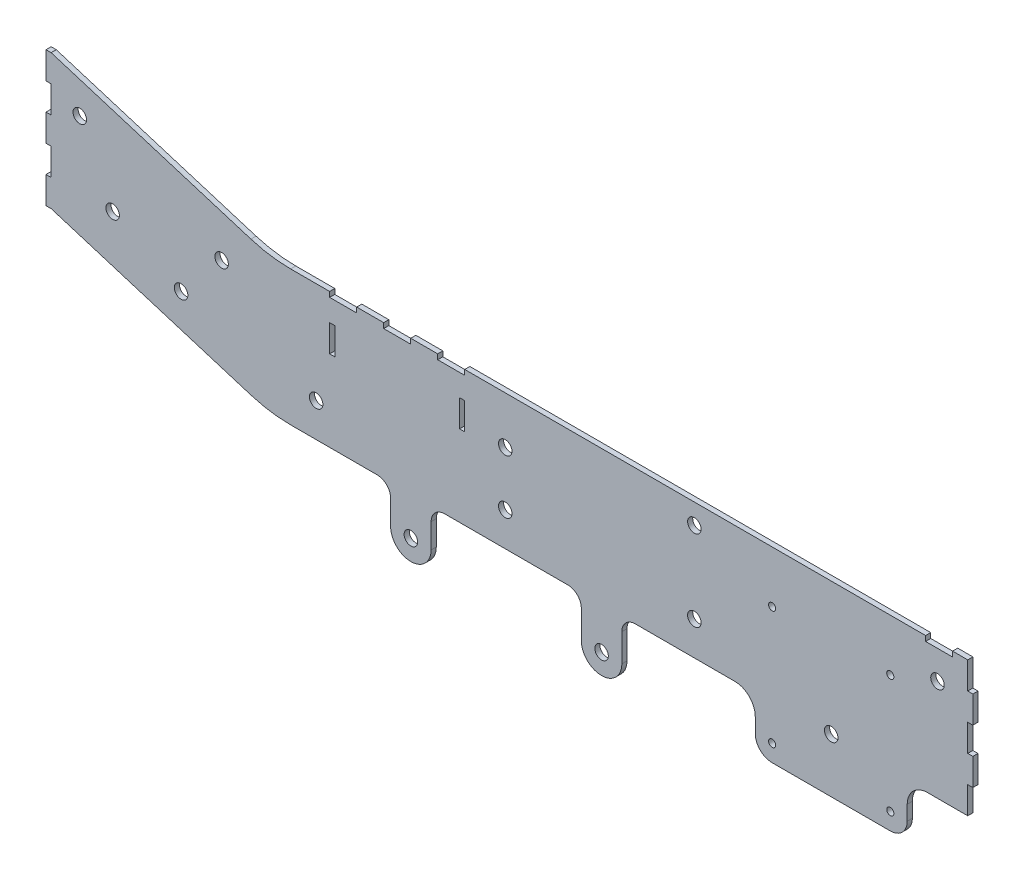
SolidWorks part; units mm, degrees
material "1060 Alloy"
ref_plane "Front Plane" through (0, 0, 0) normal (0, 0, 1) x (1, 0, 0)
ref_plane "Top Plane" through (0, 0, 0) normal (0, 1, 0) x (1, 0, 0)
ref_plane "Right Plane" through (0, 0, 0) normal (1, 0, 0) x (0, 0, -1)
sketch "Sketch2" plane through (0, 0, 0) normal (0, 0, 1) x (1, 0, 0)
  line L41 (-214.6997, -160.1998) -> (-26.8739, -218.0697)
  line L42 (10.5206, -223.6998) -> (91.8093, -223.6998)
  line L43 (104.5093, -236.3998) -> (104.5093, -259.4448)
  line L44 (142.6093, -259.4448) -> (142.6093, -236.3998)
  line L45 (155.3093, -223.6998) -> (271.0993, -223.6998)
  line L46 (283.7993, -236.3998) -> (283.7993, -262.6248)
  line L47 (321.8993, -262.6248) -> (321.8993, -236.3998)
  line L48 (334.5993, -223.6998) -> (476.2017, -223.6998)
  line L49 (561.2969, -223.6998) -> (656.7743, -223.6998)
  line L50 (656.7743, -223.6998) -> (656.7743, -198.2998)
  line L51 (656.7743, -198.2998) -> (651.9483, -198.2998)
  line L52 (651.9483, -198.2998) -> (651.9483, -172.8998)
  line L53 (651.9483, -172.8998) -> (656.7743, -172.8998)
  line L54 (656.7743, -172.8998) -> (656.7743, -147.4998)
  line L55 (656.7743, -147.4998) -> (651.9483, -147.4998)
  line L56 (651.9483, -147.4998) -> (651.9483, -122.0998)
  line L57 (651.9483, -122.0998) -> (656.7743, -122.0998)
  line L58 (656.7743, -122.0998) -> (656.7743, -96.6998)
  line L59 (656.7743, -96.6998) -> (174.1743, -96.6998)
  line L60 (174.1743, -96.6998) -> (174.1743, -101.5258)
  line L61 (174.1743, -101.5258) -> (148.7743, -101.5258)
  line L62 (148.7743, -101.5258) -> (148.7743, -96.6998)
  line L63 (148.7743, -96.6998) -> (123.3743, -96.6998)
  line L64 (123.3743, -96.6998) -> (123.3743, -101.5258)
  line L65 (123.3743, -101.5258) -> (97.9743, -101.5258)
  line L66 (97.9743, -101.5258) -> (97.9743, -96.6998)
  line L67 (97.9743, -96.6998) -> (72.5743, -96.6998)
  line L68 (72.5743, -96.6998) -> (72.5743, -101.5258)
  line L69 (72.5743, -101.5258) -> (47.1743, -101.5258)
  line L70 (47.1743, -101.5258) -> (47.1743, -96.6998)
  line L71 (47.1743, -96.6998) -> (10.5206, -96.6998)
  line L72 (-214.6997, -160.1998) -> (-26.8739, -218.0697)
  line L73 (-219.5257, -33.1998) -> (-219.5257, -58.5998)
  line L74 (-219.5257, -58.5998) -> (-214.6997, -58.5998)
  line L75 (-214.6997, -58.5998) -> (-214.6997, -83.9998)
  line L76 (-214.6997, -83.9998) -> (-219.5257, -83.9998)
  line L77 (-219.5257, -83.9998) -> (-219.5257, -109.3998)
  line L78 (-219.5257, -109.3998) -> (-214.6997, -109.3998)
  line L79 (-214.6997, -109.3998) -> (-214.6997, -134.7998)
  line L80 (-214.6997, -134.7998) -> (-219.5257, -134.7998)
  line L81 (-219.5257, -134.7998) -> (-219.5257, -160.1998)
  line L82 (-26.8739, -91.0697) -> (-214.6997, -33.1998)
  line L83 (10.5206, -223.6998) -> (91.8093, -223.6998)
  line L84 (104.5093, -236.3998) -> (104.5093, -259.4448)
  line L85 (142.6093, -259.4448) -> (142.6093, -236.3998)
  line L86 (155.3093, -223.6998) -> (271.0993, -223.6998)
  line L87 (283.7993, -236.3998) -> (283.7993, -262.6248)
  line L88 (321.8993, -262.6248) -> (321.8993, -236.3998)
  line L89 (334.5993, -223.6998) -> (476.2017, -223.6998)
  line L90 (561.2969, -223.6998) -> (656.7743, -223.6998)
  line L91 (656.7743, -223.6998) -> (656.7743, -198.2998)
  line L92 (656.7743, -198.2998) -> (651.9483, -198.2998)
  line L93 (651.9483, -198.2998) -> (651.9483, -172.8998)
  line L94 (651.9483, -172.8998) -> (656.7743, -172.8998)
  line L95 (656.7743, -172.8998) -> (656.7743, -147.4998)
  line L96 (656.7743, -147.4998) -> (651.9483, -147.4998)
  line L97 (651.9483, -147.4998) -> (651.9483, -122.0998)
  line L98 (651.9483, -122.0998) -> (656.7743, -122.0998)
  line L99 (656.7743, -122.0998) -> (656.7743, -96.6998)
  line L100 (656.7743, -96.6998) -> (174.1743, -96.6998)
  line L101 (174.1743, -96.6998) -> (174.1743, -101.5258)
  line L102 (174.1743, -101.5258) -> (148.7743, -101.5258)
  line L103 (148.7743, -101.5258) -> (148.7743, -96.6998)
  line L104 (148.7743, -96.6998) -> (123.3743, -96.6998)
  line L105 (123.3743, -96.6998) -> (123.3743, -101.5258)
  line L106 (123.3743, -101.5258) -> (97.9743, -101.5258)
  line L107 (97.9743, -101.5258) -> (97.9743, -96.6998)
  line L108 (97.9743, -96.6998) -> (72.5743, -96.6998)
  line L109 (72.5743, -96.6998) -> (72.5743, -101.5258)
  line L110 (72.5743, -101.5258) -> (47.1743, -101.5258)
  line L111 (47.1743, -101.5258) -> (47.1743, -96.6998)
  line L112 (47.1743, -96.6998) -> (10.5206, -96.6998)
  line L113 (-26.8739, -91.0697) -> (-214.6997, -33.1998)
  line L114 (-219.5257, -33.1998) -> (-219.5257, -58.5998)
  line L115 (-219.5257, -58.5998) -> (-214.6997, -58.5998)
  line L116 (-214.6997, -58.5998) -> (-214.6997, -83.9998)
  line L117 (-214.6997, -83.9998) -> (-219.5257, -83.9998)
  line L118 (-219.5257, -83.9998) -> (-219.5257, -109.3998)
  line L119 (-219.5257, -109.3998) -> (-214.6997, -109.3998)
  line L120 (-214.6997, -109.3998) -> (-214.6997, -134.7998)
  line L121 (-214.6997, -134.7998) -> (-219.5257, -134.7998)
  line L122 (-219.5257, -134.7998) -> (-219.5257, -160.1998)
  line L412 (-214.6997, -33.1998) -> (-219.5257, -33.1998)
  line L413 (-214.6997, -33.1998) -> (-219.5257, -33.1998)
  line L414 (-219.5257, -160.1998) -> (-214.6997, -160.1998)
  line L415 (-219.5257, -160.1998) -> (-214.6997, -160.1998)
  arc A11 (-26.8739, -218.0697) -> (10.5206, -223.6998) centre (10.5206, -96.6998) ccw
  arc A12 (104.5093, -236.3998) -> (91.8093, -223.6998) centre (91.8093, -236.3998) ccw
  arc A13 (104.5093, -259.4448) -> (142.6093, -259.4448) centre (123.5593, -259.4448) ccw
  arc A14 (155.3093, -223.6998) -> (142.6093, -236.3998) centre (155.3093, -236.3998) ccw
  arc A15 (283.7993, -236.3998) -> (271.0993, -223.6998) centre (271.0993, -236.3998) ccw
  arc A16 (283.7993, -262.6248) -> (321.8993, -262.6248) centre (302.8493, -262.6248) ccw
  arc A17 (334.5993, -223.6998) -> (321.8993, -236.3998) centre (334.5993, -236.3998) ccw
  arc A18 (486.8386, -229.461) -> (476.2017, -223.6998) centre (476.2017, -236.3998) ccw
  arc A19 (486.8386, -229.461) -> (550.66, -229.461) centre (518.7493, -208.6448) ccw
  arc A20 (561.2969, -223.6998) -> (550.66, -229.461) centre (561.2969, -236.3998) ccw
  arc A21 (-26.8739, -218.0697) -> (10.5206, -223.6998) centre (10.5206, -96.6998) ccw
  arc A22 (-26.8739, -91.0697) -> (10.5206, -96.6998) centre (10.5206, 30.3002) ccw
  arc A23 (104.5093, -236.3998) -> (91.8093, -223.6998) centre (91.8093, -236.3998) ccw
  arc A24 (104.5093, -259.4448) -> (142.6093, -259.4448) centre (123.5593, -259.4448) ccw
  arc A25 (155.3093, -223.6998) -> (142.6093, -236.3998) centre (155.3093, -236.3998) ccw
  arc A26 (283.7993, -236.3998) -> (271.0993, -223.6998) centre (271.0993, -236.3998) ccw
  arc A27 (283.7993, -262.6248) -> (321.8993, -262.6248) centre (302.8493, -262.6248) ccw
  arc A28 (334.5993, -223.6998) -> (321.8993, -236.3998) centre (334.5993, -236.3998) ccw
  arc A29 (486.8386, -229.461) -> (476.2017, -223.6998) centre (476.2017, -236.3998) ccw
  arc A30 (486.8386, -229.461) -> (550.66, -229.461) centre (518.7493, -208.6448) ccw
  arc A31 (561.2969, -223.6998) -> (550.66, -229.461) centre (561.2969, -236.3998) ccw
  arc A32 (-26.8739, -91.0697) -> (10.5206, -96.6998) centre (10.5206, 30.3002) ccw
  circle A56 centre (390.0743, -191.9498) radius 6.35
  circle A57 centre (390.0743, -191.9498) radius 6.35
  circle A58 centre (390.0743, -115.7498) radius 6.35
  circle A59 centre (390.0743, -115.7498) radius 6.35
  circle A60 centre (518.7493, -221.3448) radius 6.35
  circle A61 centre (518.7493, -221.3448) radius 6.35
  circle A62 centre (618.6743, -128.4498) radius 6.35
  circle A63 centre (618.6743, -128.4498) radius 6.35
  circle A64 centre (302.8493, -262.6248) radius 6.35
  circle A65 centre (302.8493, -262.6248) radius 6.35
  circle A66 centre (212.2743, -191.9498) radius 6.35
  circle A67 centre (212.2743, -191.9498) radius 6.35
  circle A68 centre (212.2743, -141.1498) radius 6.35
  circle A69 centre (212.2743, -141.1498) radius 6.35
  circle A70 centre (123.5593, -259.4448) radius 6.35
  circle A71 centre (123.5593, -259.4448) radius 6.35
  circle A72 centre (34.4743, -191.9498) radius 6.35
  circle A73 centre (34.4743, -191.9498) radius 6.35
  circle A74 centre (-92.5257, -166.5498) radius 6.35
  circle A75 centre (-92.5257, -166.5498) radius 6.35
  circle A76 centre (-156.8507, -133.7248) radius 6.35
  circle A77 centre (-156.8507, -133.7248) radius 6.35
  circle A78 centre (-54.4257, -122.0998) radius 6.35
  circle A79 centre (-54.4257, -122.0998) radius 6.35
  circle A80 centre (-187.7757, -71.2998) radius 6.35
  circle A81 centre (-187.7757, -71.2998) radius 6.35
  dimension "D1" = 0
  dimension "D2" = 0
  dimension "D3" = 0
  dimension "D4" = 0
  dimension "D5" = 0
  dimension "D6" = 0
  dimension "D7" = 0
  dimension "D8" = 0
  dimension "D9" = 0
  dimension "D10" = 0
  dimension "D11" = 0
  dimension "D12" = 0
  dimension "D13" = 0
  dimension "D14" = 0
extrude "base" add sketch "Sketch2" along normal blind 4.826
sketch "Sketch3" plane through (0, 0, 4.826) normal (0, 0, 1) x (1, 0, 0)
  line L0 (47.1743, -101.5258) -> (47.1743, -96.6998) construction
  line L1 (169.3483, -122.0998) -> (174.1743, -122.0998)
  line L2 (169.3483, -122.0998) -> (169.3483, -147.4998)
  line L3 (169.3483, -147.4998) -> (174.1743, -147.4998)
  line L4 (174.1743, -122.0998) -> (174.1743, -147.4998)
  line L5 (47.1743, -122.0998) -> (52.0003, -122.0998)
  line L6 (47.1743, -122.0998) -> (47.1743, -147.4998)
  line L7 (47.1743, -147.4998) -> (52.0003, -147.4998)
  line L8 (52.0003, -122.0998) -> (52.0003, -147.4998)
  line L9 (174.1743, -96.6998) -> (174.1743, -101.5258) construction
  line L10 (97.9743, -96.6998) -> (72.5743, -96.6998) construction
  dimension "D1" = 4.826
  dimension "D2" = 25.4
  dimension "D3" = 25.4
extrude "center support vertical holes" cut sketch "Sketch3" against normal through all
sketch "Sketch4" plane through (656.7743, 0, 0) normal (1, 0, 0) x (0, 0, -1)
  line L0 (0, -122.0998) -> (0, -96.6998) construction
  line L1 (0, -96.6998) -> (-4.826, -96.6998) construction
  line L2 (-4.826, -96.6998) -> (-4.826, -122.0998) construction
  line L3 (-4.826, -122.0998) -> (0, -122.0998) construction
  line L4 (0, -172.8998) -> (0, -147.4998) construction
  line L5 (0, -147.4998) -> (-4.826, -147.4998) construction
  line L6 (-4.826, -147.4998) -> (-4.826, -172.8998) construction
  line L7 (-4.826, -172.8998) -> (0, -172.8998) construction
  line L8 (0, -223.6998) -> (0, -198.2998) construction
  line L9 (0, -198.2998) -> (-4.826, -198.2998) construction
  line L10 (-4.826, -198.2998) -> (-4.826, -223.6998) construction
  line L11 (-4.826, -223.6998) -> (0, -223.6998) construction
  line L12 (0, -122.0998) -> (0, -96.6998)
  line L13 (0, -96.6998) -> (-4.826, -96.6998)
  line L14 (-4.826, -96.6998) -> (-4.826, -122.0998)
  line L15 (-4.826, -122.0998) -> (0, -122.0998)
  line L16 (0, -172.8998) -> (0, -147.4998)
  line L17 (0, -147.4998) -> (-4.826, -147.4998)
  line L18 (-4.826, -147.4998) -> (-4.826, -172.8998)
  line L19 (-4.826, -172.8998) -> (0, -172.8998)
  line L20 (0, -223.6998) -> (0, -198.2998)
  line L21 (0, -198.2998) -> (-4.826, -198.2998)
  line L22 (-4.826, -198.2998) -> (-4.826, -223.6998)
  line L23 (-4.826, -223.6998) -> (0, -223.6998)
extrude "Cut-Extrude2" cut sketch "Sketch4" against normal blind 9.652
sketch "Sketch5" plane through (0, 0, 0) normal (0, 0, 1) x (1, 0, 0)
  line L0 (463.2122, -272.4369) -> (574.3372, -272.4369)
  line L1 (447.3372, -256.5619) -> (447.3372, -242.7498)
  line L3 (590.2122, -256.5619) -> (590.2122, -242.7498)
  line L43 (647.1223, -198.2998) -> (651.9483, -198.2998)
  line L44 (651.9483, -198.2998) -> (651.9483, -172.8998)
  line L45 (651.9483, -172.8998) -> (647.1223, -172.8998)
  line L46 (647.1223, -172.8998) -> (647.1223, -147.4998)
  line L47 (647.1223, -147.4998) -> (651.9483, -147.4998)
  line L48 (651.9483, -147.4998) -> (651.9483, -122.0998)
  line L49 (651.9483, -122.0998) -> (647.1223, -122.0998)
  line L50 (647.1223, -122.0998) -> (647.1223, -96.6998)
  line L51 (647.1223, -96.6998) -> (174.1743, -96.6998)
  line L52 (174.1743, -96.6998) -> (174.1743, -101.5258)
  line L53 (174.1743, -101.5258) -> (148.7743, -101.5258)
  line L54 (148.7743, -101.5258) -> (148.7743, -96.6998)
  line L55 (148.7743, -96.6998) -> (123.3743, -96.6998)
  line L56 (123.3743, -96.6998) -> (123.3743, -101.5258)
  line L57 (123.3743, -101.5258) -> (97.9743, -101.5258)
  line L58 (97.9743, -101.5258) -> (97.9743, -96.6998)
  line L59 (97.9743, -96.6998) -> (72.5743, -96.6998)
  line L60 (72.5743, -96.6998) -> (72.5743, -101.5258)
  line L61 (72.5743, -101.5258) -> (47.1743, -101.5258)
  line L62 (47.1743, -101.5258) -> (47.1743, -96.6998)
  line L63 (47.1743, -96.6998) -> (10.5206, -96.6998)
  line L64 (-26.8739, -91.0697) -> (-214.6997, -33.1998)
  line L65 (-214.6997, -33.1998) -> (-219.5257, -33.1998)
  line L66 (-219.5257, -33.1998) -> (-219.5257, -58.5998)
  line L67 (-219.5257, -58.5998) -> (-214.6997, -58.5998)
  line L68 (-214.6997, -58.5998) -> (-214.6997, -83.9998)
  line L69 (-214.6997, -83.9998) -> (-219.5257, -83.9998)
  line L70 (-219.5257, -83.9998) -> (-219.5257, -109.3998)
  line L71 (-219.5257, -109.3998) -> (-214.6997, -109.3998)
  line L72 (-214.6997, -109.3998) -> (-214.6997, -134.7998)
  line L73 (-214.6997, -134.7998) -> (-219.5257, -134.7998)
  line L74 (-219.5257, -134.7998) -> (-219.5257, -160.1998)
  line L75 (-219.5257, -160.1998) -> (-214.6997, -160.1998)
  line L76 (-214.6997, -160.1998) -> (-26.8739, -218.0697)
  line L77 (10.5206, -223.6998) -> (91.8093, -223.6998)
  line L78 (104.5093, -236.3998) -> (104.5093, -259.4448)
  line L79 (142.6093, -259.4448) -> (142.6093, -236.3998)
  line L80 (155.3093, -223.6998) -> (271.0993, -223.6998)
  line L81 (283.7993, -236.3998) -> (283.7993, -262.6248)
  line L82 (321.8993, -262.6248) -> (321.8993, -236.3998)
  line L83 (334.5993, -223.6998) -> (476.2017, -223.6998)
  line L84 (561.2969, -223.6998) -> (647.1223, -223.6998)
  line L85 (647.1223, -223.6998) -> (647.1223, -198.2998)
  line L86 (647.1223, -198.2998) -> (651.9483, -198.2998)
  line L87 (651.9483, -198.2998) -> (651.9483, -172.8998)
  line L88 (651.9483, -172.8998) -> (647.1223, -172.8998)
  line L89 (647.1223, -172.8998) -> (647.1223, -147.4998)
  line L90 (647.1223, -147.4998) -> (651.9483, -147.4998)
  line L91 (651.9483, -147.4998) -> (651.9483, -122.0998)
  line L92 (651.9483, -122.0998) -> (647.1223, -122.0998)
  line L93 (647.1223, -122.0998) -> (647.1223, -96.6998)
  line L94 (647.1223, -96.6998) -> (174.1743, -96.6998)
  line L95 (174.1743, -96.6998) -> (174.1743, -101.5258)
  line L96 (174.1743, -101.5258) -> (148.7743, -101.5258)
  line L97 (148.7743, -101.5258) -> (148.7743, -96.6998)
  line L98 (148.7743, -96.6998) -> (123.3743, -96.6998)
  line L99 (123.3743, -96.6998) -> (123.3743, -101.5258)
  line L100 (123.3743, -101.5258) -> (97.9743, -101.5258)
  line L101 (97.9743, -101.5258) -> (97.9743, -96.6998)
  line L102 (97.9743, -96.6998) -> (72.5743, -96.6998)
  line L103 (72.5743, -96.6998) -> (72.5743, -101.5258)
  line L104 (72.5743, -101.5258) -> (47.1743, -101.5258)
  line L105 (47.1743, -101.5258) -> (47.1743, -96.6998)
  line L106 (47.1743, -96.6998) -> (10.5206, -96.6998)
  line L107 (-26.8739, -91.0697) -> (-214.6997, -33.1998)
  line L108 (-214.6997, -33.1998) -> (-219.5257, -33.1998)
  line L109 (-219.5257, -33.1998) -> (-219.5257, -58.5998)
  line L110 (-219.5257, -58.5998) -> (-214.6997, -58.5998)
  line L111 (-214.6997, -58.5998) -> (-214.6997, -83.9998)
  line L112 (-214.6997, -83.9998) -> (-219.5257, -83.9998)
  line L113 (-219.5257, -83.9998) -> (-219.5257, -109.3998)
  line L114 (-219.5257, -109.3998) -> (-214.6997, -109.3998)
  line L115 (-214.6997, -109.3998) -> (-214.6997, -134.7998)
  line L116 (-214.6997, -134.7998) -> (-219.5257, -134.7998)
  line L117 (-219.5257, -134.7998) -> (-219.5257, -160.1998)
  line L118 (-219.5257, -160.1998) -> (-214.6997, -160.1998)
  line L119 (-214.6997, -160.1998) -> (-26.8739, -218.0697)
  line L120 (10.5206, -223.6998) -> (91.8093, -223.6998)
  line L121 (104.5093, -236.3998) -> (104.5093, -259.4448)
  line L122 (142.6093, -259.4448) -> (142.6093, -236.3998)
  line L123 (155.3093, -223.6998) -> (271.0993, -223.6998)
  line L124 (283.7993, -236.3998) -> (283.7993, -262.6248)
  line L125 (321.8993, -262.6248) -> (321.8993, -236.3998)
  line L126 (334.5993, -223.6998) -> (476.2017, -223.6998)
  line L127 (561.2969, -223.6998) -> (647.1223, -223.6998)
  line L128 (647.1223, -223.6998) -> (647.1223, -198.2998)
  circle A0 centre (574.3372, -256.5619) radius 3.3528 construction
  circle A1 centre (463.2122, -256.5619) radius 3.3528 construction
  circle A2 centre (463.2122, -145.4369) radius 3.3528 construction
  circle A3 centre (574.3372, -145.4369) radius 3.2512 construction
  circle A4 centre (574.3372, -256.5619) radius 3.3528
  circle A5 centre (463.2122, -256.5619) radius 3.3528
  circle A6 centre (463.2122, -145.4369) radius 3.3528
  circle A7 centre (574.3372, -145.4369) radius 3.2512
  arc A8 (447.3372, -256.5619) -> (463.2122, -272.4369) centre (463.2122, -256.5619) ccw
  arc A9 (574.3372, -272.4369) -> (590.2122, -256.5619) centre (574.3372, -256.5619) ccw
  arc A10 (447.3372, -242.7498) -> (428.2872, -223.6998) centre (428.2872, -242.7498) ccw
  arc A11 (609.2622, -223.6998) -> (590.2122, -242.7498) centre (609.2622, -242.7498) ccw
  arc A21 (-26.8739, -91.0697) -> (10.5206, -96.6998) centre (10.5206, 30.3002) ccw
  arc A22 (-26.8739, -218.0697) -> (10.5206, -223.6998) centre (10.5206, -96.6998) ccw
  arc A23 (104.5093, -236.3998) -> (91.8093, -223.6998) centre (91.8093, -236.3998) ccw
  arc A24 (104.5093, -259.4448) -> (142.6093, -259.4448) centre (123.5593, -259.4448) ccw
  arc A25 (155.3093, -223.6998) -> (142.6093, -236.3998) centre (155.3093, -236.3998) ccw
  arc A26 (283.7993, -236.3998) -> (271.0993, -223.6998) centre (271.0993, -236.3998) ccw
  arc A27 (283.7993, -262.6248) -> (321.8993, -262.6248) centre (302.8493, -262.6248) ccw
  arc A28 (334.5993, -223.6998) -> (321.8993, -236.3998) centre (334.5993, -236.3998) ccw
  arc A29 (486.8386, -229.461) -> (476.2017, -223.6998) centre (476.2017, -236.3998) ccw
  arc A30 (486.8386, -229.461) -> (550.66, -229.461) centre (518.7493, -208.6448) ccw
  arc A31 (561.2969, -223.6998) -> (550.66, -229.461) centre (561.2969, -236.3998) ccw
  arc A32 (-26.8739, -91.0697) -> (10.5206, -96.6998) centre (10.5206, 30.3002) ccw
  arc A33 (-26.8739, -218.0697) -> (10.5206, -223.6998) centre (10.5206, -96.6998) ccw
  arc A34 (104.5093, -236.3998) -> (91.8093, -223.6998) centre (91.8093, -236.3998) ccw
  arc A35 (104.5093, -259.4448) -> (142.6093, -259.4448) centre (123.5593, -259.4448) ccw
  arc A36 (155.3093, -223.6998) -> (142.6093, -236.3998) centre (155.3093, -236.3998) ccw
  arc A37 (283.7993, -236.3998) -> (271.0993, -223.6998) centre (271.0993, -236.3998) ccw
  arc A38 (283.7993, -262.6248) -> (321.8993, -262.6248) centre (302.8493, -262.6248) ccw
  arc A39 (334.5993, -223.6998) -> (321.8993, -236.3998) centre (334.5993, -236.3998) ccw
  arc A40 (486.8386, -229.461) -> (476.2017, -223.6998) centre (476.2017, -236.3998) ccw
  arc A41 (486.8386, -229.461) -> (550.66, -229.461) centre (518.7493, -208.6448) ccw
  arc A42 (561.2969, -223.6998) -> (550.66, -229.461) centre (561.2969, -236.3998) ccw
  arc M56 (455.2747, -263.7056) -> (456.0685, -264.4994) centre (456.0685, -263.7056) ccw
  line M57 (456.0685, -264.4994) -> (581.481, -264.4994)
  arc M58 (581.481, -264.4994) -> (582.2747, -263.7056) centre (581.481, -263.7056) ccw
  line M59 (582.2747, -263.7056) -> (582.2747, -138.2931)
  line M63 (455.2747, -138.2931) -> (455.2747, -263.7056)
  circle M64 centre (480.5665, -220.0494) radius 5.5626
  circle M68 centre (463.2122, -256.5619) radius 3.3528
  circle M70 centre (574.3372, -256.5619) radius 3.3528
  circle M74 centre (556.9829, -220.0494) radius 5.5626
  dimension "D2" = 31.75
  dimension "D3" = 19.05
  dimension "D1" = 0
extrude "Boss-Extrude1" add sketch "Sketch5" along normal through all contours A11 L127 L126 A10 L1 A8 L0 A9 L3 M59 M58 M57 M56 M63 | L127 A42 A41 A40 L126 M74 M64 M63 M56 M57 M58 M59 M70 M68 | A40 M64 | A42 M74 region at (453.3122, -266.4619, 0) region at (518.7816, -247.2481, 0) region at (479.3181, -224.7256, 0) region at (558.2159, -224.7224, 0)
sketch "Sketch6" plane through (0, 0, 4.826) normal (0, 0, 1) x (1, 0, 0)
  circle A0 centre (463.1868, -145.4369) radius 3.3528 construction
  circle A2 centre (463.1868, -145.4369) radius 3.3528
  circle A3 centre (574.3118, -145.4369) radius 3.3528 construction
  circle A4 centre (574.3118, -145.4369) radius 3.3528
extrude "Cut-Extrude3" cut sketch "Sketch6" against normal through all
sketch "Sketch7" plane through (0, -96.6998, 0) normal (0, 1, 0) x (1, 0, 0)
  line L0 (647.1223, -4.826) -> (174.1743, -4.826) construction
  line L1 (632.8983, -4.826) -> (607.4983, -4.826)
  line L2 (632.8983, -4.826) -> (632.8983, 0)
  line L3 (632.8983, 0) -> (607.4983, 0)
  line L4 (607.4983, -4.826) -> (607.4983, 0)
  line L5 (647.1223, 0) -> (174.1743, 0) construction
  line L6 (651.9483, -4.826) -> (651.9483, 0) construction
  dimension "D1" = 25.4
  dimension "D2" = 19.05
extrude "Cut-Extrude4" cut sketch "Sketch7" against normal blind 4.826
equation "\"sheet width\"= .19"
equation "\"width\"= 24.5"
equation "\"length\"= 34.5"
equation "\"standoff hole size\"= .5"
equation "\"ground clearence\"= 3"
equation "\"small drive pulley\"= 74.55mm"
equation "\"large drive pulley\"= 150.95mm"
equation "\"drive axle hole size\"= .5"
equation "\"front pulley clearence\"= 1"
equation "\"center support location\"= 19"
equation "\"D1@Sketch3\"=\"sheet width\""
equation "\"D1@base\"=\"sheet width\""
equation "\"D1@Cut-Extrude2\"=\"sheet width\"*2"
equation "\"D1@Cut-Extrude4\"=\"sheet width\""
